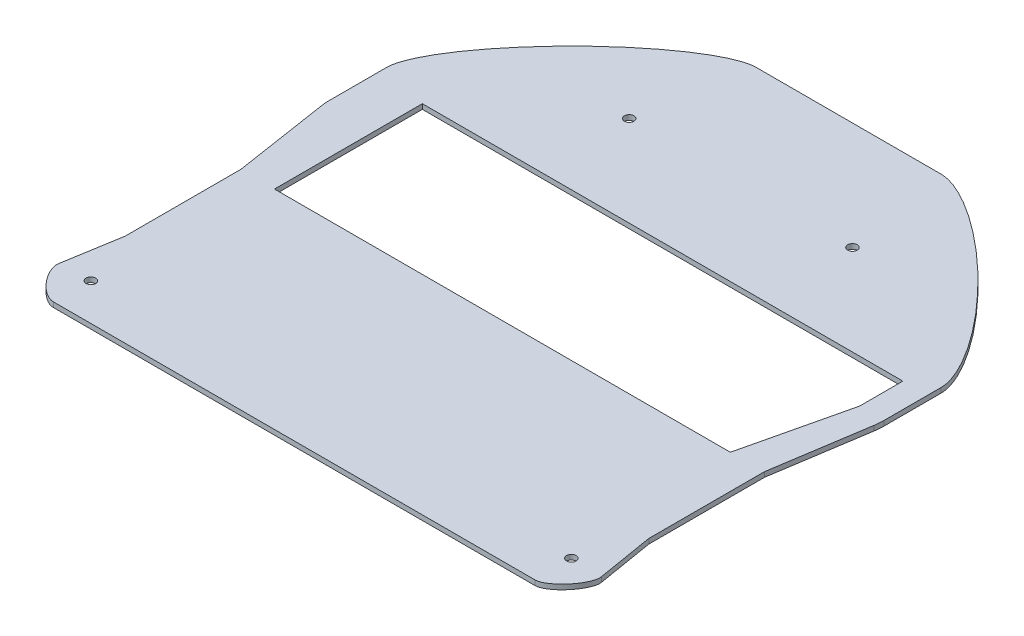
SolidWorks part; units mm, degrees
ref_plane "Front Plane" through (0, 0, 0) normal (0, 0, 1) x (1, 0, 0)
ref_plane "Top Plane" through (0, 0, 0) normal (0, 1, 0) x (1, 0, 0)
ref_plane "Right Plane" through (0, 0, 0) normal (1, 0, 0) x (0, 0, -1)
sketch "Sketch1" plane through (0, 0, 0) normal (0, 1, 0) x (1, 0, 0)
  line L0 (-90, 180) -> (-90, 0) construction
  line L1 (-180, 180) -> (0, 180)
  line L2 (-180, 180) -> (-180, 0)
  line L3 (-180, 0) -> (0, 0)
  line L4 (0, 180) -> (0, 0)
  line L5 (-180, 90) -> (0, 90) construction
  line L6 (-180, 30) -> (0, 30)
  line L7 (-130, 30) -> (-50, 30)
  line L8 (-130, 30) -> (-130, -30)
  line L9 (-130, -30) -> (-50, -30)
  line L10 (-50, 30) -> (-50, -30)
  line L11 (-130, 30) -> (-50, -30) construction
  line L12 (-130, -30) -> (-50, 30) construction
  dimension "D1" = 180
  dimension "D2" = 180
  dimension "D3" = 60
  dimension "D4" = 80
extrude "Boss-Extrude1" add sketch "Sketch1" along normal blind 1.6 contours L10 L3 L8 L9 | L2 L6 L4 L1 | L6 L10 L3 L4 | L8 L6 L2 L3 | L10 L6 L8 L3 region at (-90, 0, -105) region at (-155, 0, -15) region at (-25, 0, -15) region at (-90, 0, -15) region at (-90, 0, 15)
sketch "Sketch2" plane through (0, 1.6, 0) normal (0, 1, 0) x (1, 0, 0)
  line L0 (-180, 30) -> (0, 30)
  line L1 (-180, 180) -> (-180, 0) construction
  line L2 (0, 180) -> (0, 0) construction
  line L3 (-180, 180) -> (0, 180) construction
  line L4 (-90, 180) -> (-90, -30) construction
  line L5 (-130, -30) -> (-50, -30) construction
  dimension "D1" = 150
sketch "Sketch3" plane through (0, 1.6, 0) normal (0, 1, 0) x (1, 0, 0)
  line L0 (-180, 122) -> (0, 122)
  line L1 (-180, 180) -> (-180, 0) construction
  line L2 (0, 180) -> (0, 0) construction
  line L3 (-180, 30) -> (0, 30) construction
  dimension "D1" = 92
sketch "Sketch5" plane through (0, 1.6, 0) normal (0, 1, 0) x (1, 0, 0)
  line L0 (-114, 180) -> (-114, -30)
  line L1 (-180, 180) -> (0, 180) construction
  line L2 (-130, -30) -> (-50, -30) construction
  line L3 (-90, 180) -> (-90, -30) construction
  dimension "D1" = 24
fillet "Fillet1" radius 60 2 edges at (0, 0.8, -180) (-180, 0.8, -180) conic rho 0.2
sketch "Sketch6" plane through (0, 1.6, 0) normal (0, 1, 0) x (1, 0, 0)
  line L0 (-50, 0) -> (-130, 0)
  line L1 (-130, 0) -> (-130, -30)
  line L2 (-130, -30) -> (-50, -30)
  line L3 (-50, -30) -> (-50, 0)
  line L4 (-180, 0) -> (-175, 30.1113)
  line L5 (-175, 30.1113) -> (-175, 67.7113)
  line L6 (-175, 67.7113) -> (-180, 100)
  line L7 (-180, 120) -> (-180, 0) construction
  line L8 (-90, 180) -> (-90, -30) construction
  line L10 (-90, 180) -> (-90, 0) construction
  line L11 (0, 0) -> (-5, 30.1113)
  line L12 (-5, 30.1113) -> (-5, 67.7113)
  line L13 (-5, 67.7113) -> (0, 100)
  line M3 (0, 0) -> (0, 120)
  line M7 (-180, 120) -> (-180, 0)
  line M9 (-130, 0) -> (-130, -30)
  line M10 (-130, -30) -> (-50, -30)
  line M11 (-50, -30) -> (-50, 0)
  dimension "D1" = 37.6
  dimension "D2" = 85
  dimension "D3" = 100
extrude "Cut-Extrude1" cut sketch "Sketch6" against normal blind 10 contours L0 M11 M9 M10 | L5 L6 L4 M7 | L13 L12 L11 M3 region at (-90, 1.6, 15) region at (-177.8779, 1.6, -49.5379) region at (-2.1221, 1.6, -49.5379)
fillet "Fillet2" radius 10 2 edges at (-180, 0.8, 0) (0, 0.8, 0) conic rho 0.25
fillet "Fillet3" radius 20 2 edges at (-180, 0.8, -100) (0, 0.8, -100)
sketch "Sketch9" plane through (0, 1.6, 0) normal (0, 1, 0) x (1, 0, 0)
  line L0 (-175, 67.6) -> (-5, 67.6) construction
  line L1 (-175, 30.1113) -> (-175, 67.7113) construction
  line L2 (-5, 30.1113) -> (-5, 67.7113) construction
  line L3 (-180, 30) -> (0, 30) construction
  line L4 (-180, 115.6) -> (0, 115.6) construction
  line L5 (-180, 120) -> (-180, 101.5394) construction
  line L6 (0, 120) -> (0, 101.5394) construction
  line L7 (-16, 115.6) -> (-16, 67.6) construction
  line L8 (-90, 180) -> (-90, -30) construction
  line L9 (-164, 115.6) -> (-164, 67.6)
  line L10 (0, 101.5394) -> (-16, 101.5394) construction
  line L11 (-8, 101.5394) -> (-8, 115.6)
  line L12 (-164, 115.6) -> (-8, 115.6)
  line L14 (-16, 67.6) -> (-164, 67.6)
  line L16 (-8, 101.5394) -> (-16, 67.6)
  dimension "D1" = 37.6
  dimension "D2" = 48
  dimension "D3" = 74
  dimension "D4" = 74
extrude "Cut-Extrude3" cut sketch "Sketch9" against normal up to next
sketch "Sketch11" plane through (0, 1.6, 0) normal (0, 1, 0) x (1, 0, 0)
  line L0 (-168.2026, 0) -> (-11.7974, 0) construction
  line L1 (-175, 30.1113) -> (-175, 67.7113) construction
  line L2 (-114, 180) -> (-114, -30) construction
  line L3 (-180, 122) -> (0, 122) construction
  line L4 (-90, 180) -> (-90, 0) construction
  circle A0 centre (-168, 12) radius 1.55
  circle A1 centre (-126.25, 145) radius 1.55
  circle A2 centre (-12, 12) radius 1.55
  circle A3 centre (-53.75, 145) radius 1.55
  dimension "D1" = 3.1
  dimension "D2" = 12
  dimension "D4" = 3.1
  dimension "D5" = 12.25
  dimension "D6" = 23
  dimension "D3" = 7
extrude "Cut-Extrude5" cut sketch "Sketch11" against normal up to next
